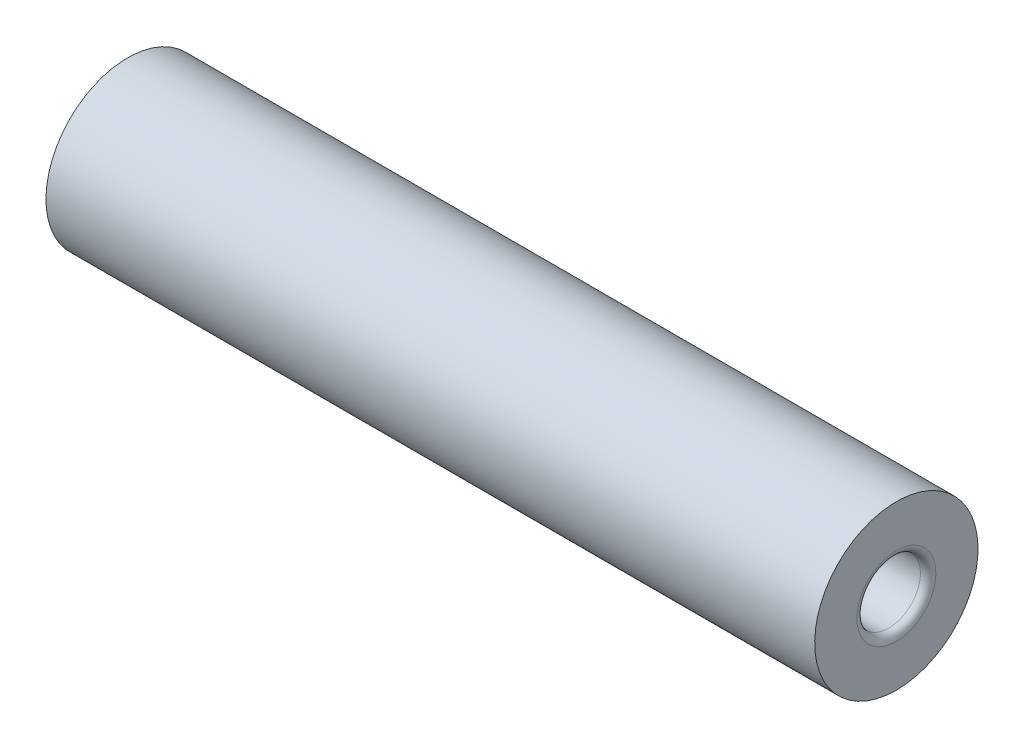
SolidWorks part; units mm, degrees
ref_plane "Front Plane" through (0, 0, 0) normal (0, 0, 1) x (1, 0, 0)
ref_plane "Top Plane" through (0, 0, 0) normal (0, 1, 0) x (1, 0, 0)
ref_plane "Right Plane" through (0, 0, 0) normal (1, 0, 0) x (0, 0, -1)
sketch "Sketch1" plane through (0, 0, 0) normal (0, 0, 1) x (1, 0, 0)
  line L1 (0, 0) -> (50.8, 0) construction
  line L2 (0, 0) -> (0, 5.3975)
  line L3 (0, 5.3975) -> (50.8, 5.3975)
  line L4 (50.8, 0) -> (50.8, 5.3975)
  line L5 (25.4, 5.3975) -> (25.4, 0) construction
  line L7 (12.9075, 0) -> (0, 0)
  line L8 (37.8925, 0) -> (50.8, 0)
  line L11 (12.9075, 0) -> (37.8925, 0)
  point P208 (25.4, 1.5)
  dimension "D1" = 50.8
  dimension "D2" = 5.3975
revolve "Revolve1" add sketch "Sketch1" angle 360 about L3
sketch "Sketch4" plane through (0, 0, 0) normal (-1, 0, 0) x (0, 0, 1)
  point P0 (0, 5.3975)
hole_wizard "Tap Drill for M4 Helicoil1" positions "Sketch5" profile "Sketch6" hole size "M4x0.7" standard "ANSI Metric"
sketch "Sketch5" plane through (0, 0, 0) normal (-1, 0, 0) x (0, 0, 1)
  point P0 (0, 5.3975)
sketch "Sketch6" plane through (0, 5.3975, 0) normal (0, 1, 0) x (0, 0, 1)
  line L0 (0, 0) -> (0, 10.1518)
  line L1 (0, 10.1518) -> (2.1, 8.89)
  line L2 (2.1, 8.89) -> (2.1, 0)
  line L5 (2.1, 0) -> (0, 0)
  line L10 (0, 10.1518) -> (-2.1, 8.89) construction
  line L11 (0, -6.35) -> (0, 107.95) construction
  dimension "Hole Dia." = 4.2
  dimension "Hole Depth" = 8.89
  dimension "Drill Angle" = 118
ref_plane "Plane1" through (25.4, 0, 0) normal (-1, 0, 0) x (0, 0, 1)
mirror "Mirror1" about plane through (25.4, 0, 0) normal (-1, 0, 0) of "Tap Drill for M4 Helicoil1"
fillet "Fillet1" radius 0.508 2 edges at (0, 5.3975, 2.1) (50.8, 5.3975, -2.1)
equation "\"arm spacing\"= 2"
equation "\"D1@Sketch1\"=\"arm spacing\""
equation "\"D2@Sketch1\"=\"roller diameter\"/2"
equation "\"symbol room\"= ( ( 35 / 2 ) - 6.5 )"
equation "\"roller diameter\"= .425"
